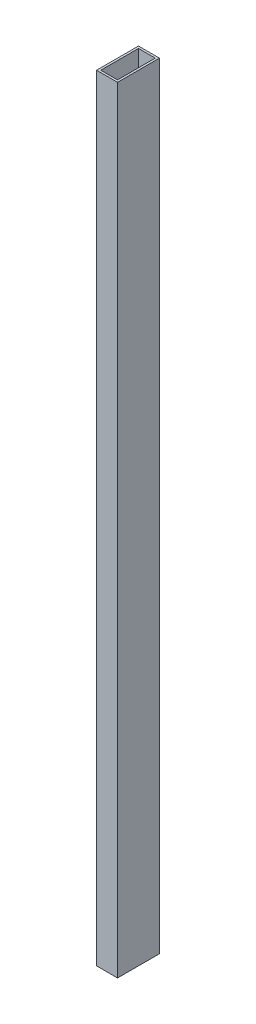
SolidWorks part; units mm, degrees
ref_plane "Спереди" through (0, 0, 0) normal (0, 0, 1) x (1, 0, 0)
ref_plane "Сверху" through (0, 0, 0) normal (0, 1, 0) x (1, 0, 0)
ref_plane "Справа" through (0, 0, 0) normal (1, 0, 0) x (0, 0, -1)
sketch "Эскиз1" plane through (0, 0, 0) normal (0, 1, 0) x (1, 0, 0)
  line L1 (-10, 20) -> (10, 20)
  line L2 (-10, 20) -> (-10, -20)
  line L3 (-10, -20) -> (10, -20)
  line L4 (10, 20) -> (10, -20)
  line L5 (-10, 20) -> (10, -20) construction
  line L6 (-10, -20) -> (10, 20) construction
  point P0 (0, 0)
extrude "Вытянуть-Тонкостенный1" add sketch "Эскиз1" along normal blind 740 thin thin type one direction reverse wall 2
